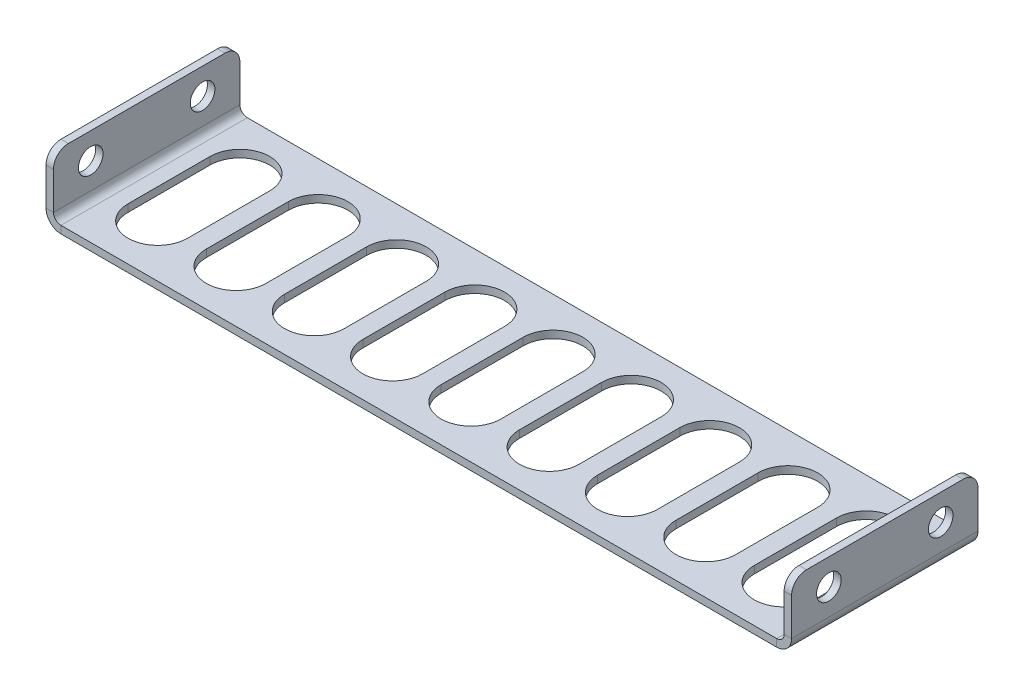
SolidWorks part; units mm, degrees
note: The reader was unsure of these and kept them because the rebuilt part matched: bend radius of "基体折弯1", "基体折弯2".
material "6061 合金"
ref_plane "前视基准面" through (0, 0, 0) normal (0, 0, 1) x (1, 0, 0)
ref_plane "上视基准面" through (0, 0, 0) normal (0, 1, 0) x (1, 0, 0)
ref_plane "右视基准面" through (0, 0, 0) normal (1, 0, 0) x (0, 0, -1)
sketch "草图1" plane through (0, 0, 0) normal (0, 0, 1) x (1, 0, 0)
  line L0 (-49, 8) -> (-49, 0)
  line L1 (-49, 0) -> (49, 0)
  line L2 (49, 0) -> (49, 8)
  dimension "D1" = 8
  dimension "D2" = 98
base flange "基体-法兰1" sketch "草图1" end condition mid plane depth 25 reverse direction no thickness 1 reverse thickness direction no bend radius 1
bend "基体折弯1" bend radius 1 bend angle 90 parameters "D5"=1
bend "基体折弯2" bend radius 1 bend angle 90 parameters "D5"=2
sketch "草图6" plane through (0, 0, 0) normal (1, 0, 0) x (0, 0, -1)
  line L0 (-12.5, 8) -> (12.5, 8) construction
  line L1 (0, 4.5) -> (0, 0) construction
  line L5 (-7.5, 4.5) -> (7.5, 4.5) construction
  circle A0 centre (-7.5, 4.5) radius 1.65
  circle A1 centre (7.5, 4.5) radius 1.65
  dimension "D3" = 3.3
  dimension "D1" = 15
  dimension "D2" = 3.5
extrude "切除-拉伸1" cut sketch "草图6" against normal through all both and the other way through all
sketch "草图7" plane through (0, -1, 0) normal (0, -1, 0) x (1, 0, 0)
  line L0 (42, 5.5) -> (42, -5.5) construction
  line L3 (46, 5.5) -> (46, -5.5)
  line L14 (38, 5.5) -> (38, -5.5)
  line L17 (-42, 5.5) -> (-42, -5.5) construction
  line L18 (-38, 5.5) -> (-38, -5.5)
  line L19 (-46, 5.5) -> (-46, -5.5)
  line L20 (-48, -12.5) -> (48, -12.5) construction
  line L21 (-48, 12.5) -> (48, 12.5) construction
  line L22 (-31.5, 5.5) -> (-31.5, -5.5) construction
  line L23 (-27.5, 5.5) -> (-27.5, -5.5)
  line L24 (-35.5, 5.5) -> (-35.5, -5.5)
  line L25 (-21, 5.5) -> (-21, -5.5) construction
  line L26 (-17, 5.5) -> (-17, -5.5)
  line L27 (-25, 5.5) -> (-25, -5.5)
  line L28 (-10.5, 5.5) -> (-10.5, -5.5) construction
  line L29 (-6.5, 5.5) -> (-6.5, -5.5)
  line L30 (-14.5, 5.5) -> (-14.5, -5.5)
  line L31 (0, 5.5) -> (0, -5.5) construction
  line L32 (4, 5.5) -> (4, -5.5)
  line L33 (-4, 5.5) -> (-4, -5.5)
  line L34 (10.5, 5.5) -> (10.5, -5.5) construction
  line L35 (14.5, 5.5) -> (14.5, -5.5)
  line L36 (6.5, 5.5) -> (6.5, -5.5)
  line L37 (21, 5.5) -> (21, -5.5) construction
  line L38 (25, 5.5) -> (25, -5.5)
  line L39 (17, 5.5) -> (17, -5.5)
  line L40 (31.5, 5.5) -> (31.5, -5.5) construction
  line L41 (35.5, 5.5) -> (35.5, -5.5)
  line L42 (27.5, 5.5) -> (27.5, -5.5)
  arc A14 (-38, 5.5) -> (-46, 5.5) centre (-42, 5.5) ccw
  arc A15 (-46, -5.5) -> (-38, -5.5) centre (-42, -5.5) ccw
  arc A16 (-27.5, 5.5) -> (-35.5, 5.5) centre (-31.5, 5.5) ccw
  arc A17 (-35.5, -5.5) -> (-27.5, -5.5) centre (-31.5, -5.5) ccw
  arc A18 (-17, 5.5) -> (-25, 5.5) centre (-21, 5.5) ccw
  arc A19 (-25, -5.5) -> (-17, -5.5) centre (-21, -5.5) ccw
  arc A20 (-6.5, 5.5) -> (-14.5, 5.5) centre (-10.5, 5.5) ccw
  arc A21 (-14.5, -5.5) -> (-6.5, -5.5) centre (-10.5, -5.5) ccw
  arc A22 (4, 5.5) -> (-4, 5.5) centre (0, 5.5) ccw
  arc A23 (-4, -5.5) -> (4, -5.5) centre (0, -5.5) ccw
  arc A24 (14.5, 5.5) -> (6.5, 5.5) centre (10.5, 5.5) ccw
  arc A25 (6.5, -5.5) -> (14.5, -5.5) centre (10.5, -5.5) ccw
  arc A26 (25, 5.5) -> (17, 5.5) centre (21, 5.5) ccw
  arc A27 (17, -5.5) -> (25, -5.5) centre (21, -5.5) ccw
  arc A28 (35.5, 5.5) -> (27.5, 5.5) centre (31.5, 5.5) ccw
  arc A29 (27.5, -5.5) -> (35.5, -5.5) centre (31.5, -5.5) ccw
  arc A30 (46, 5.5) -> (38, 5.5) centre (42, 5.5) ccw
  arc A31 (38, -5.5) -> (46, -5.5) centre (42, -5.5) ccw
  point P2 (-42, 0)
  point P7 (-42, -9.5)
  point P10 (-42, 9.5)
  point P17 (-31.5, 0)
  point P24 (-21, 0)
  point P31 (-10.5, 0)
  point P38 (0, 0)
  point P47 (10.5, 0)
  point P54 (21, 0)
  point P61 (31.5, 0)
  point P66 (42, 0)
  dimension "D4" = 9
  dimension "D5" = 2.5
  dimension "D1" = 3
  dimension "D2" = 3
  dimension "D3" = 8
extrude "切除-拉伸2" cut sketch "草图7" against normal blind 10
fillet "圆角1" radius 2 4 edges at (49.5, 8, 12.5) (49.5, 8, -12.5) (-49.5, 8, -12.5) (-49.5, 8, 12.5)
sketch "折弯-线1" [suppressed] plane through (0, 0, 0) normal (0, 1, 0) x (1, 0, 0)
sketch "边界框1" [suppressed] plane through (0, 0, 0) normal (0, 1, 0) x (1, 0, 0)
sheet metal parameters "钣金6" thickness 1 parameters "D1"=1
flat pattern "平板型式6" [suppressed]
sketch "折弯-线2" plane through (0, 0, 0) normal (0, 1, 0) x (1, 0, 0)
sketch "边界框2" [suppressed] plane through (0, 0, 0) normal (0, 1, 0) x (1, 0, 0)
bend of the flat pattern "展平-<基体折弯1>1"
bend of the flat pattern "展平-<基体折弯2>1"
sheet metal parameters "钣金7" thickness 1 parameters "D1"=1
flat pattern "平板型式6" [suppressed]
sketch "折弯-线2" plane through (0, 0, 0) normal (0, 1, 0) x (1, 0, 0)
sketch "边界框2" [suppressed] plane through (0, 0, 0) normal (0, 1, 0) x (1, 0, 0)
bend of the flat pattern "展平-<基体折弯1>1"
bend of the flat pattern "展平-<基体折弯2>1"
sheet metal parameters "钣金8" thickness 1 parameters "D1"=1
flat pattern "平板型式6"
sketch "折弯-线2" plane through (0, 0, 0) normal (0, 1, 0) x (1, 0, 0)
  line L0 (-49.1781, -12.5) -> (-49.1781, 12.5) construction
  line L1 (49.1781, 12.5) -> (49.1781, -12.5) construction
  line L2 (-49.1781, -12.5) -> (-49.1781, 12.5) construction
  line L3 (49.1781, 12.5) -> (49.1781, -12.5) construction
sketch3d "边界框2" [suppressed]
  line L0 (-8.3562, 0.0001, 0) -> (106.3562, 0, 0) construction
  line L1 (-8.3562, 25, 0) -> (106.3562, 24.9999, 0) construction
  line L2 (-8.3562, 0.0001, 0) -> (-8.3562, 25, 0) construction
  line L3 (106.3562, 0, 0) -> (106.3562, 24.9999, 0) construction
bend of the flat pattern "展平-<基体折弯1>1"
bend of the flat pattern "展平-<基体折弯2>1"
